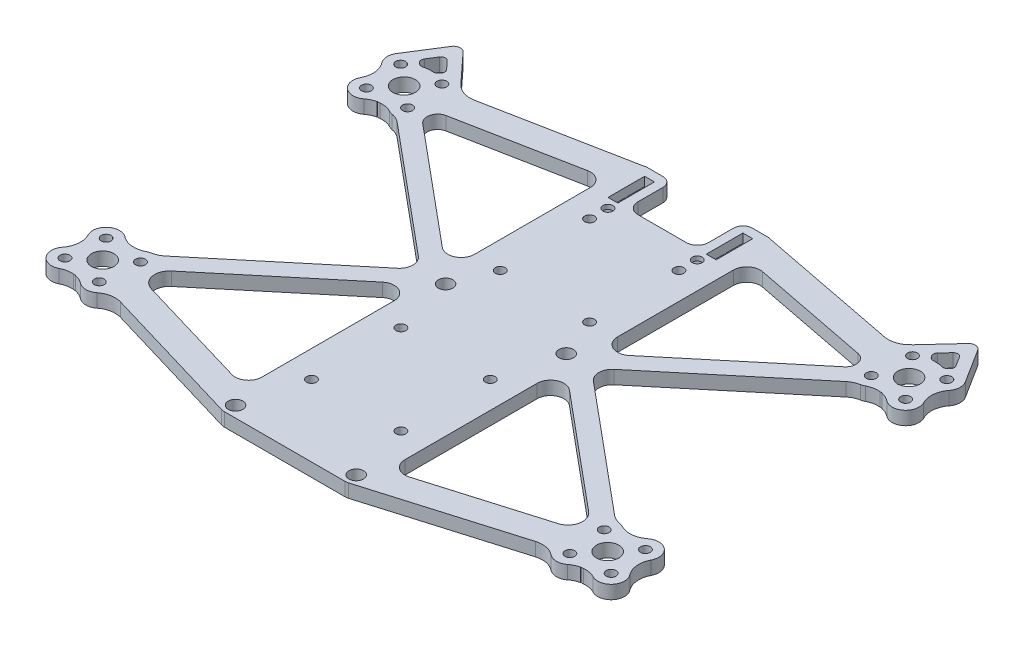
SolidWorks part; units mm, degrees
ref_plane "Front Plane" through (0, 0, 0) normal (0, 0, 1) x (1, 0, 0)
ref_plane "Top Plane" through (0, 0, 0) normal (0, 1, 0) x (1, 0, 0)
ref_plane "Right Plane" through (0, 0, 0) normal (1, 0, 0) x (0, 0, -1)
sketch "Sketch1" plane through (0, 0, 0) normal (0, 1, 0) x (1, 0, 0)
  line L0 (0, 42.225) -> (0, -42.225) construction
  line L1 (16, 42.225) -> (-16, 42.225)
  line L2 (16, 42.225) -> (16, -42.225)
  line L3 (16, -42.225) -> (-16, -42.225)
  line L4 (-16, 42.225) -> (-16, -42.225)
  line L5 (16, 42.225) -> (-16, -42.225) construction
  line L6 (16, -42.225) -> (-16, 42.225) construction
  line L12 (-12.1, 50.425) -> (-12.1, 52.425) construction
  line L17 (-11, 52.425) -> (-11, 42.225) construction
  line L18 (-7.9, 42.225) -> (-14.1, 42.225)
  line L20 (-10, 36) -> (10, 36)
  line L21 (-10, 36) -> (-10, 16)
  line L22 (-10, 16) -> (10, 16)
  line L23 (10, 36) -> (10, 16)
  line L24 (-10, 36) -> (10, 16) construction
  line L25 (-10, 16) -> (10, 36) construction
  line L26 (-14.5, 10.775) -> (14.5, 10.775)
  line L27 (-14.5, 10.775) -> (-14.5, 41.225)
  line L28 (-14.5, 41.225) -> (14.5, 41.225)
  line L29 (14.5, 10.775) -> (14.5, 41.225)
  line L30 (-14.5, 10.775) -> (14.5, 41.225) construction
  line L31 (-14.5, 41.225) -> (14.5, 10.775) construction
  line L32 (-10, -6.225) -> (10, -6.225)
  line L33 (-10, -6.225) -> (-10, -26.225)
  line L34 (-10, -26.225) -> (10, -26.225)
  line L35 (10, -6.225) -> (10, -26.225)
  line L36 (-10, -6.225) -> (10, -26.225) construction
  line L37 (-10, -26.225) -> (10, -6.225) construction
  line L38 (-15.75, -36.225) -> (15.75, -36.225)
  line L39 (-15.75, -36.225) -> (-15.75, 3.775)
  line L40 (-15.75, 3.775) -> (15.75, 3.775)
  line L41 (15.75, -36.225) -> (15.75, 3.775)
  line L42 (-15.75, -36.225) -> (15.75, 3.775) construction
  line L43 (-15.75, 3.775) -> (15.75, -36.225) construction
  line L48 (-7.9, 42.225) -> (-7.9, 52.425)
  line L49 (-7.9, 52.425) -> (-14.1, 52.425)
  line L59 (-14.1, 42.225) -> (-14.1, 52.425)
  line L63 (-12.1, 50.425) -> (-9.9, 50.425)
  line L64 (-12.1, 50.425) -> (-12.1, 42.225)
  line L65 (-12.1, 42.225) -> (-9.9, 42.225)
  line L66 (-9.9, 50.425) -> (-9.9, 42.225)
  line L67 (-12.1, 50.425) -> (-9.9, 42.225) construction
  line L68 (-12.1, 42.225) -> (-9.9, 50.425) construction
  line L69 (-12.1, 50.425) -> (-14.1, 50.425) construction
  line L74 (7.9, 42.225) -> (14.1, 42.225)
  line L75 (14.1, 42.225) -> (14.1, 52.425)
  line L76 (7.9, 52.425) -> (14.1, 52.425)
  line L77 (7.9, 42.225) -> (7.9, 52.425)
  line L78 (12.1, 50.425) -> (9.9, 50.425)
  line L79 (12.1, 50.425) -> (12.1, 42.225)
  line L80 (12.1, 42.225) -> (9.9, 42.225)
  line L81 (9.9, 50.425) -> (9.9, 42.225)
  line L82 (-14.5, 10.775) -> (-14.5, 3.775) construction
  line L83 (-14.5, 7.275) -> (16, 7.275) construction
  line L89 (-13.5, -37.225) -> (-16, -37.225) construction
  line L94 (-14.1, 52.425) -> (-16, 52.425)
  line L95 (-14.1, 52.425) -> (-14.1, 42.225)
  line L96 (-14.1, 42.225) -> (-16, 42.225)
  line L97 (-16, 52.425) -> (-16, 42.225)
  line L98 (14.1, 52.425) -> (16, 52.425)
  line L99 (14.1, 52.425) -> (14.1, 42.225)
  line L100 (14.1, 42.225) -> (16, 42.225)
  line L101 (16, 52.425) -> (16, 42.225)
  circle A3 centre (-10, 36) radius 1.1
  circle A4 centre (10, 36) radius 1.1
  circle A5 centre (10, 16) radius 1.1
  circle A6 centre (-10, 16) radius 1.1
  circle A7 centre (-10, -6.225) radius 1.1
  circle A8 centre (10, -6.225) radius 1.1
  circle A9 centre (10, -26.225) radius 1.1
  circle A10 centre (-10, -26.225) radius 1.1
  circle A37 centre (-13.5, 7.275) radius 2.5
  circle A38 centre (-13.5, 7.275) radius 1.625
  circle A39 centre (13.5, 7.275) radius 1.625
  circle A40 centre (-13.5, -39.725) radius 2.5
  circle A41 centre (-13.5, -39.725) radius 1.625
  circle A42 centre (13.5, -39.725) radius 1.625
  point P0 (0, 0)
  point P8 (0, 0)
  point P16 (0, 26)
  point P26 (0, 26)
  point P31 (0, -16.225)
  point P36 (0, -16.225)
  point P61 (-11, 46.325)
  dimension "D3" = 2
  dimension "D17" = 2.2
  dimension "D22" = 5
  dimension "D23" = 3.25
  dimension "D8" = 32
  dimension "D9" = 22
  dimension "D10" = 20
  dimension "D11" = 29
  dimension "D12" = 30.45
  dimension "D13" = 40
  dimension "D14" = 31.5
  dimension "D15" = 1
  dimension "D16" = 7
  dimension "D18" = 2.2
  dimension "D20" = 8.2
  dimension "D24" = 1
extrude "Base shape" add sketch "Sketch1" along normal blind 2 contours L63 L66 L1 L48 L49 L59 L18 L64 | L81 L78 L79 L1 L75 L76 L77 | L94 L97 L1 L59 | L101 L98 L75 L1 | L1 L4 L3 L2 | A4 | A3 | A7 | A8 | A9 | A10 | A5 | A6 | A39 | A38 | A41 | A42 region at (15.05, 0, -47.325) region at (13.1, 0, -42.3444) region at (-8.9, 0, -42.3444) region at (-15.05, 0, -47.325)
sketch "Sketch2" plane through (0, 0, 0) normal (0, -1, 0) x (1, 0, 0)
  line L0 (-12.1, -42.225) -> (-9.9, -50.425) construction
  line L1 (12.1, -42.225) -> (9.9, -50.425) construction
  line L4 (12.1, -42.225) -> (9.9, -42.225)
  line L5 (12.1, -50.425) -> (12.1, -42.225)
  line L6 (9.9, -50.425) -> (12.1, -50.425)
  line L7 (9.9, -42.225) -> (9.9, -50.425)
  line L8 (12.1, -42.225) -> (9.9, -42.225)
  line L9 (12.1, -50.425) -> (12.1, -42.225)
  line L10 (9.9, -50.425) -> (12.1, -50.425)
  line L11 (9.9, -42.225) -> (9.9, -50.425)
  line L12 (-9.9, -42.225) -> (-12.1, -42.225)
  line L13 (-9.9, -50.425) -> (-9.9, -42.225)
  line L14 (-12.1, -50.425) -> (-9.9, -50.425)
  line L15 (-12.1, -42.225) -> (-12.1, -50.425)
  line L16 (-9.9, -42.225) -> (-12.1, -42.225)
  line L17 (-9.9, -50.425) -> (-9.9, -42.225)
  line L18 (-12.1, -50.425) -> (-9.9, -50.425)
  line L19 (-12.1, -42.225) -> (-12.1, -50.425)
  circle A0 centre (-11, -46.325) radius 1.1
  circle A1 centre (11, -46.325) radius 1.1
  dimension "D1" = 0
  dimension "D2" = 0
extrude "Camera mount pockets" add sketch "Sketch2" against normal offset from surface (1 mm away) 1 contours A0 L19 | A0 L17 | A1 L9 | A1 L11 region at (11, 0, -43.8523) region at (11, 0, -48.7977) region at (-11, 0, -43.8523) region at (-11, 0, -48.7977) up to face at (11, 2, -46.325)
fillet "Main fillets" radius 2.5 6 edges at (7.9, 1, -42.225) (-7.9, 1, -42.225) (-16, 1, -52.425) (16, 1, -52.425) (-16, 1, 42.225) (16, 1, 42.225)
fillet "Inner camera mount fillets" radius 2.1 2 edges at (-7.9, 1, -52.425) (7.9, 1, -52.425)
sketch "Sketch3" plane through (0, 2, 0) normal (0, 1, 0) x (1, 0, 0)
  line L6 (12.1, 42.225) -> (12.1, 50.425)
  line L7 (9.9, 42.225) -> (12.1, 42.225)
  line L8 (-10, 52.425) -> (-13.5, 52.425)
  line L9 (-16, 49.925) -> (-16, -39.725)
  line L10 (-13.5, -42.225) -> (13.5, -42.225)
  line L11 (16, -39.725) -> (16, 49.925)
  line L12 (13.5, 52.425) -> (10, 52.425)
  line L13 (7.9, 50.325) -> (7.9, 44.725)
  line L14 (5.4, 42.225) -> (-5.4, 42.225)
  line L15 (-7.9, 44.725) -> (-7.9, 50.325)
  line L16 (-10, 52.425) -> (-13.5, 52.425)
  line L17 (-16, 49.925) -> (-16, -39.725)
  line L18 (-13.5, -42.225) -> (13.5, -42.225)
  line L19 (16, -39.725) -> (16, 49.925)
  line L20 (13.5, 52.425) -> (10, 52.425)
  line L21 (7.9, 50.325) -> (7.9, 44.725)
  line L22 (5.4, 42.225) -> (-5.4, 42.225)
  line L23 (-7.9, 44.725) -> (-7.9, 50.325)
  line L24 (9.9, 50.425) -> (9.9, 42.225)
  line L25 (12.1, 50.425) -> (9.9, 50.425)
  line L26 (12.1, 42.225) -> (12.1, 50.425)
  line L27 (9.9, 42.225) -> (12.1, 42.225)
  line L28 (9.9, 50.425) -> (9.9, 42.225)
  line L29 (12.1, 50.425) -> (9.9, 50.425)
  line L30 (-9.9, 42.225) -> (-9.9, 50.425)
  line L31 (-12.1, 42.225) -> (-9.9, 42.225)
  line L32 (-12.1, 50.425) -> (-12.1, 42.225)
  line L33 (-9.9, 50.425) -> (-12.1, 50.425)
  line L34 (-9.9, 42.225) -> (-9.9, 50.425)
  line L35 (-12.1, 42.225) -> (-9.9, 42.225)
  line L36 (-12.1, 50.425) -> (-12.1, 42.225)
  line L37 (-9.9, 50.425) -> (-12.1, 50.425)
  circle A0 centre (13.5, -39.725) radius 1.625 construction
  circle A1 centre (-13.5, -39.725) radius 1.625 construction
  circle A2 centre (-13.5, 7.275) radius 1.625 construction
  circle A3 centre (-10, -6.225) radius 1.1 construction
  circle A4 centre (-10, -26.225) radius 1.1 construction
  circle A5 centre (10, -26.225) radius 1.1 construction
  circle A6 centre (10, -6.225) radius 1.1 construction
  circle A7 centre (13.5, 7.275) radius 1.625 construction
  arc A8 (-13.5, 52.425) -> (-16, 49.925) centre (-13.5, 49.925) ccw
  arc A9 (-16, -39.725) -> (-13.5, -42.225) centre (-13.5, -39.725) ccw
  arc A10 (13.5, -42.225) -> (16, -39.725) centre (13.5, -39.725) ccw
  arc A11 (16, 49.925) -> (13.5, 52.425) centre (13.5, 49.925) ccw
  arc A12 (-7.9, 50.325) -> (-10, 52.425) centre (-10, 50.325) ccw
  arc A13 (5.4, 42.225) -> (7.9, 44.725) centre (5.4, 44.725) ccw
  arc A14 (-7.9, 44.725) -> (-5.4, 42.225) centre (-5.4, 44.725) ccw
  arc A15 (-7.9, 50.325) -> (-10, 52.425) centre (-10, 50.325) ccw
  arc A16 (-13.5, 52.425) -> (-16, 49.925) centre (-13.5, 49.925) ccw
  arc A17 (-16, -39.725) -> (-13.5, -42.225) centre (-13.5, -39.725) ccw
  arc A18 (13.5, -42.225) -> (16, -39.725) centre (13.5, -39.725) ccw
  arc A19 (16, 49.925) -> (13.5, 52.425) centre (13.5, 49.925) ccw
  arc A21 (5.4, 42.225) -> (7.9, 44.725) centre (5.4, 44.725) ccw
  arc A22 (-7.9, 44.725) -> (-5.4, 42.225) centre (-5.4, 44.725) ccw
  circle A24 centre (-10, 16) radius 1.1 construction
  circle A25 centre (-10, 36) radius 1.1 construction
  circle A26 centre (10, 36) radius 1.1 construction
  circle A27 centre (10, 16) radius 1.1 construction
  circle A28 centre (10, 16) radius 1.1
  circle A29 centre (10, 36) radius 1.1
  circle A30 centre (-10, 36) radius 1.1
  circle A31 centre (-10, 16) radius 1.1
  circle A32 centre (13.5, 7.275) radius 1.625
  circle A33 centre (10, -6.225) radius 1.1
  circle A34 centre (10, -26.225) radius 1.1
  circle A35 centre (-10, -26.225) radius 1.1
  circle A36 centre (-10, -6.225) radius 1.1
  circle A37 centre (13.5, -39.725) radius 1.625
  circle A38 centre (-13.5, -39.725) radius 1.625
  circle A39 centre (-13.5, 7.275) radius 1.625
  arc A48 (10, 52.425) -> (7.9, 50.325) centre (10, 50.325) ccw
  arc A49 (10, 52.425) -> (7.9, 50.325) centre (10, 50.325) ccw
  dimension "D1" = 0
  dimension "D2" = 0
  dimension "D3" = 0
extrude "Thicker base" add sketch "Sketch3" along normal blind 1
sketch "Sketch4" plane through (0, 0, 0) normal (0, -1, 0) x (1, 0, 0)
  line L0 (0, 13.9568) -> (0, -8.6953) construction
  line L1 (-14.1, -38.5) -> (-5.9, -38.5)
  line L2 (-14.1, -38.5) -> (-14.1, -41.7)
  line L3 (-14.1, -41.7) -> (-5.9, -41.7)
  line L4 (-5.9, -38.5) -> (-5.9, -41.7)
  line L5 (-10, -38.5) -> (-10, -41.7) construction
  line L7 (14.1, -38.5) -> (5.9, -38.5)
  line L8 (14.1, -38.5) -> (14.1, -41.7)
  line L9 (14.1, -41.7) -> (5.9, -41.7)
  line L10 (5.9, -38.5) -> (5.9, -41.7)
  line L11 (-14.1, -38.5) -> (-10.9, -41.7) construction
  line L12 (-14.1, -40.1) -> (-5.9, -40.1) construction
  circle A0 centre (-10, -36) radius 2
  circle A1 centre (-13.3929, -39.2071) radius 1
  circle A2 centre (-13.3929, -40.9929) radius 1
  circle A3 centre (-6.6071, -39.2071) radius 1
  circle A4 centre (-6.6071, -40.9929) radius 1
  circle A5 centre (6.6071, -40.9929) radius 1
  circle A6 centre (6.6071, -39.2071) radius 1
  circle A7 centre (13.3929, -39.2071) radius 1
  circle A8 centre (13.3929, -40.9929) radius 1
  point P9 (-10, -38)
  dimension "D5" = 4
  dimension "D7" = 2
  dimension "D1" = 8.2
  dimension "D2" = 3.2
  dimension "D3" = 10
  dimension "D4" = 0.5
  dimension "D6" = 45
extrude "Battery holder pockets" cut sketch "Sketch4" against normal offset from surface (2 mm away) 1 contours A2 L2 | A2 L3 | L2 A1 | L1 A1 | A3 L4 | A3 L1 | L4 A4 | L3 A4 | A5 L9 | A5 L10 | L10 A6 | L7 A6 | A7 L7 | A7 L8 | L8 A8 | L9 A8 | L3 L4 L1 L2 | L9 L10 L7 L8 region at (-13.3929, 0, -38.3812) region at (-14.2188, 0, -39.2071) region at (-6.6071, 0, -38.3812) region at (-14.2188, 0, -40.9929) region at (-5.7812, 0, -39.2071) region at (-13.3929, 0, -41.8188) region at (-6.6071, 0, -41.8188) region at (-5.7812, 0, -40.9929) region at (14.2188, 0, -39.2071) region at (13.3929, 0, -38.3812) region at (6.6071, 0, -38.3812) region at (14.2188, 0, -40.9929) region at (5.7812, 0, -39.2071) region at (13.3929, 0, -41.8188) region at (6.6071, 0, -41.8188) region at (5.7812, 0, -40.9929) up to face at (-13.5, 3, 41.35)
sketch "Sketch5" plane through (0, 2, 0) normal (0, -1, 0) x (1, 0, 0)
  line L0 (-10, -38.5) -> (-10, -41.7) construction
  line L1 (-12.6858, -38.5) -> (-7.3142, -38.5) construction
  line L2 (-12.6858, -41.7) -> (-7.3142, -41.7) construction
  line L3 (0, 5.9884) -> (0, -5.6723) construction
  circle A0 centre (-10, -40.1) radius 1.1
  circle A1 centre (10, -40.1) radius 1.1
  dimension "D1" = 2.2
extrude "Battery holder holes" cut sketch "Sketch5" against normal up to next
sketch "Sketch6" [suppressed] plane through (0, 0, 0) normal (0, -1, 0) x (1, 0, 0)
  line L0 (0, -5.1) -> (0, 9.653) construction
  line L8 (-13.5, -7.275) -> (13.5, -7.275) construction
  line L10 (-16, -23.775) -> (16, -23.775) construction
  line L11 (-16, -49.925) -> (-16, 39.725) construction
  line L12 (16, -49.925) -> (16, 39.725) construction
  line L13 (17.5, -32.275) -> (19, -32.275)
  line L14 (16, -35.275) -> (19, -35.275)
  line L15 (16, -35.275) -> (16, -12.275)
  line L16 (16, -12.275) -> (19, -12.275)
  line L17 (19, -35.275) -> (19, -12.275)
  line L18 (16, -35.275) -> (19, -12.275) construction
  line L19 (16, -12.275) -> (19, -35.275) construction
  line L20 (16, -33.775) -> (17.5, -33.775)
  line L21 (16, -33.775) -> (16, -13.775)
  line L22 (16, -13.775) -> (17.5, -13.775)
  line L23 (17.5, -33.775) -> (17.5, -13.775)
  line L24 (16, -33.775) -> (17.5, -13.775) construction
  line L25 (16, -13.775) -> (17.5, -33.775) construction
  line L26 (17.5, -15.275) -> (19, -15.275)
  line L27 (-17.5, -32.275) -> (-19, -32.275)
  line L28 (-17.5, -15.275) -> (-19, -15.275)
  line L29 (-16, -33.775) -> (-16, -13.775)
  line L30 (-16, -33.775) -> (-17.5, -33.775)
  line L31 (-17.5, -33.775) -> (-17.5, -13.775)
  line L32 (-16, -13.775) -> (-17.5, -13.775)
  line L33 (-16, -35.275) -> (-16, -12.275)
  line L34 (-16, -35.275) -> (-19, -35.275)
  line L35 (-19, -35.275) -> (-19, -12.275)
  line L36 (-16, -12.275) -> (-19, -12.275)
  line L37 (16, 20.725) -> (19, 20.725)
  line L38 (16, 20.725) -> (16, -2.275)
  line L39 (16, -2.275) -> (19, -2.275)
  line L40 (19, 20.725) -> (19, -2.275)
  line L41 (16, 19.225) -> (17.5, 19.225)
  line L42 (16, 19.225) -> (16, -0.775)
  line L43 (16, -0.775) -> (17.5, -0.775)
  line L44 (17.5, 19.225) -> (17.5, -0.775)
  line L45 (17.5, 0.725) -> (19, 0.725)
  line L46 (17.5, 17.725) -> (19, 17.725)
  line L47 (-17.5, 17.725) -> (-19, 17.725)
  line L48 (-17.5, 0.725) -> (-19, 0.725)
  line L49 (-16, 19.225) -> (-16, -0.775)
  line L50 (-16, 19.225) -> (-17.5, 19.225)
  line L51 (-17.5, 19.225) -> (-17.5, -0.775)
  line L52 (-16, -0.775) -> (-17.5, -0.775)
  line L53 (-16, 20.725) -> (-16, -2.275)
  line L54 (-16, 20.725) -> (-19, 20.725)
  line L55 (-19, 20.725) -> (-19, -2.275)
  line L56 (-16, -2.275) -> (-19, -2.275)
  point P19 (17.5, -23.775)
  point P25 (16.75, -23.775)
  line M18 (16, -49.925) -> (16, 39.725)
  line M22 (-16, 39.725) -> (-16, -49.925)
  dimension "D1" = 10
  dimension "D4" = 23
  dimension "D5" = 3
  dimension "D6" = 1.5
  dimension "D7" = 20
  dimension "D8" = 1.5
extrude "Strap holders" [suppressed] add sketch "Sketch6" against normal up to surface (2 mm away) contours L23 L20 L14 L17 L13 M18 | L23 L26 L17 L16 L22 M18 | L45 L44 L43 L39 L40 M18 | L44 L46 L40 L37 L38 L41 | L54 L55 L47 L51 L50 M22 | L56 L52 L51 L48 L55 M22 | L36 L35 L28 L31 L32 M22 | L35 L34 L30 L31 L27 M22 up to face at (-10, 2, -41.2)
fillet "Strap holder fillets" [suppressed] radius 0.75
sketch "Sketch7" plane through (0, 3, 0) normal (0, 1, 0) x (1, 0, 0)
  line L0 (-56.5, 41) -> (-16, 48.8822) construction
  line L1 (56.5, -41) -> (-56.5, -41)
  line L2 (56.5, -41) -> (56.5, 41)
  line L3 (56.5, 41) -> (-56.5, 41)
  line L4 (-56.5, -41) -> (-56.5, 41)
  line L5 (56.5, -41) -> (-56.5, 41) construction
  line L6 (56.5, 41) -> (-56.5, -41) construction
  line L7 (-16, 49.925) -> (-16, -39.725) construction
  line L8 (-55.9269, 38.0553) -> (-15.4269, 45.9374)
  line L9 (-48.7441, 45.5657) -> (-13.5, 52.425)
  line L10 (-57.0731, 43.9447) -> (-16.5731, 51.8269) construction
  line L11 (-13.5, 7.275) -> (13.5, 7.275) construction
  line L12 (-62.2591, 34.0839) -> (-50.7409, 47.9161) construction
  line L13 (-56.5, 41) -> (-16, 7.275) construction
  line L14 (-57.7798, 39.4631) -> (-17.2798, 5.7381)
  line L15 (-55.2202, 42.5369) -> (-14.7202, 8.8119)
  line L16 (-17.2798, 5.7381) -> (-16, 4.6724)
  line L17 (-56.5, 41) -> (-61.1107, 44.8394) construction
  line L18 (-56.5, 50) -> (-56.5, 32) construction
  line L19 (-61.1107, 44.8394) -> (-52.6606, 45.6107) construction
  line L20 (-56.8857, 45.2251) -> (-57.6128, 53.192) construction
  line L21 (-58.8813, 53.9926) -> (-63.553, 46.5906)
  line L22 (-56.5103, 54.209) -> (-50.5757, 47.7751)
  line L23 (-57.4765, 51.6982) -> (-60.0373, 47.6408)
  line L24 (-57.4765, 51.6982) -> (-54.2235, 48.1715)
  line L25 (-57.7798, -24.9131) -> (-17.2798, 8.8119)
  line L26 (-55.2202, -27.9869) -> (-14.7202, 5.7381)
  line L27 (-56.5, -26.45) -> (-16, -38.462) construction
  line L28 (-49.218, -31.7389) -> (-14.2109, -42.1218)
  line L29 (-55.647, -23.5738) -> (-15.147, -35.5858)
  line L30 (-57.353, -29.3262) -> (-16.853, -41.3382) construction
  circle A0 centre (-56.5, 41) radius 38.1
  circle A1 centre (-56.5, 41) radius 9
  circle A2 centre (-56.5, 41) radius 6
  circle A3 centre (-52.6606, 45.6107) radius 1.1
  circle A4 centre (-60.3394, 36.3893) radius 1.1
  circle A5 centre (-61.1107, 44.8394) radius 1.1
  circle A6 centre (-51.8893, 37.1606) radius 1.1
  circle A7 centre (-61.1107, 44.8394) radius 3
  circle A8 centre (-52.6606, 45.6107) radius 3
  circle A9 centre (-60.3394, 36.3893) radius 3
  circle A10 centre (-51.8893, 37.1606) radius 3
  circle A12 centre (-56.5, 41) radius 2.5
  circle A13 centre (-57.6128, 53.192) radius 1.5
  circle A14 centre (-67.319, 40.0125) radius 4.864
  circle A15 centre (-55.5125, 30.181) radius 4.864
  circle A16 centre (-46.7947, 50.9004) radius 4.864
  circle A17 centre (-53.3325, 29.4302) radius 4.864
  circle A18 centre (-45.6353, 37.6419) radius 2.3718
  circle A20 centre (-56.5, -26.45) radius 6
  circle A21 centre (-51.8893, -22.6106) radius 1.1
  circle A22 centre (-60.3394, -21.8393) radius 1.1
  circle A23 centre (-61.1107, -30.2894) radius 1.1
  circle A24 centre (-52.6606, -31.0607) radius 1.1
  circle A25 centre (-52.6606, -31.0607) radius 3
  circle A26 centre (-51.8893, -22.6106) radius 3
  circle A27 centre (-56.5, -26.45) radius 2.5
  circle A28 centre (-61.1107, -30.2894) radius 3
  circle A29 centre (-67.319, -25.4625) radius 4.864
  circle A30 centre (-60.3394, -21.8393) radius 3
  circle A31 centre (-55.5125, -15.631) radius 4.864
  circle A32 centre (-53.3325, -14.8802) radius 4.864
  circle A34 centre (-56.5, -26.45) radius 9
  circle A35 centre (-57.4875, -37.269) radius 4.864
  arc A37 (-16, -39.725) -> (-13.5, -42.225) centre (-13.5, -39.725) ccw construction
  circle A38 centre (-47.7979, -37.1938) radius 4.8259
  circle A39 centre (-44.585, -23.4182) radius 3.2947
  point P0 (0, 0)
  point P36 (-51.8893, 37.1606)
  point P54 (-57.4765, 51.6982)
  arc M23 (-13.5, 52.425) -> (-16, 49.925) centre (-13.5, 49.925) ccw
  line M24 (-16, 49.925) -> (-16, -39.725)
  arc M25 (-16, -39.725) -> (-13.5, -42.225) centre (-13.5, -39.725) ccw
  dimension "D3" = 76.2
  dimension "D4" = 12
  dimension "D5" = 3
  dimension "D10" = 2.2
  dimension "D11" = 5
  dimension "D12" = 3
  dimension "D1" = 113
  dimension "D2" = 82
  dimension "D13" = 8
  dimension "D6" = 3
  dimension "D7" = 3
  dimension "D8" = 2
  dimension "D9" = 2
  dimension "D14" = 3
  dimension "D15" = 3
extrude "Arms" add sketch "Sketch7" against normal up to surface (3 mm away) contours A13 | A13 L21 A1 L23 | A13 L24 A1 L22 | A12 L15 L3 A2 A8 A7 A9 L4 L14 | A10 L14 L4 A2 | A12 L4 L14 A10 L15 L3 | A12 L3 L15 | A10 A2 L3 L15 | A7 L23 A1 | A8 A1 L24 | A14 A2 A7 | A14 A9 A2 | A15 L4 A2 A9 | A15 A10 A2 | A8 A2 L3 A1 | A16 A1 L9 | A1 L3 L8 A0 L9 | A10 L8 A1 L3 A2 | A10 L15 A1 L8 | A10 A1 L15 | A10 L14 A1 | A17 A1 L14 A10 | A1 L14 A0 L15 | A17 L14 A1 | A0 L14 L16 L15 M24 | A0 L8 L9 M24 M23 | A1 L8 L3 | A18 L8 A1 | A18 A1 L15 | L25 A34 L26 L16 L14 | L29 A34 L28 L1 M25 M24 | A34 L29 A26 A20 A25 | A34 L26 A26 L29 | A38 L28 A34 | A34 A26 L26 | A34 L25 A26 | A32 A34 L25 | A34 A32 A26 L25 | A26 A31 A20 | L4 A31 A30 A20 | A20 A30 A28 L4 A27 L25 | L25 A26 A20 L4 | A20 A31 L4 | L4 A27 L26 A26 L25 | L26 A27 L4 A20 A25 A26 | A35 A25 A20 L4 | A35 A20 A28 | A20 A29 A28 | A20 A30 A29 | A39 L26 A34 | A39 A34 L29 | L25 A27 L4 | L1 L28 M25 | A7 | A5 | A8 | A3 | A10 | A6 | A9 | A4 | A25 | A24 | A26 | A21 | A28 | A23 | A30 | A22 region at (-16.139, 3, 41.3276) region at (-32.0548, 3, 33.7211) region at (-48.9183, 3, 32.3052) region at (-17.512, 3, -48.8664) region at (-21.642, 3, -11.8743) region at (-49.1658, 3, 28.1048) region at (-47.1131, 3, 25.7411) region at (-33.5979, 3, 7.3867) region at (-45.287, 3, -40.5598) region at (-33.1819, 3, -45.6059) region at (-38.4384, 3, -25.9598) region at (-48.6014, 3, 24.4797) region at (-47.909, 3, 22.4325) region at (-49.0457, 3, -40.2446) region at (-49.1442, 3, -43.1485) region at (-47.3222, 3, -39.4546) region at (-48.0479, 3, -36.9785) region at (-55.5626, 3, 32.6566) region at (-48.8372, 3, 22.0461) region at (-51.6653, 3, -40.5782) region at (-51.9373, 3, -41.1697) region at (-48.3887, 3, -46.1037) region at (-48.5353, 3, -38.5539) region at (-48.8372, 3, -36.5961) region at (-50.8649, 3, -33.6569) region at (-58.5204, 3, 32.3845) region at (-53.3964, 3, 28.1246) region at (-50.7815, 3, 19.7112) region at (-50.8649, 3, 19.1069) region at (-54.4455, 3, -39.1872) region at (-53.806, 3, -41.1887) region at (-50.7815, 3, -34.2612) region at (-51.5106, 3, -34.0266) region at (-62.7022, 3, 27.3626) region at (-58.1278, 3, 31.2511) region at (-54.4187, 3, 24.7209) region at (-51.5106, 3, 19.4766) region at (-54.8114, 3, -50.9666) region at (-62.4345, 3, 24.4296) region at (-53.9078, 3, -49.0743) region at (-57.6128, 3, -53.192) region at (-57.4374, 3, 20.2434) region at (-57.4374, 3, -34.7934) region at (-54.4796, 3, -35.0655) region at (-56.5422, 3, 23.9165) region at (-55.689, 3, 21.824) region at (-54.4796, 3, 20.5155) region at (-55.689, 3, -36.374) region at (-60.5112, 3, -48.4716) region at (-59.9651, 3, -50.4962) region at (-56.3638, 3, 20.4356) region at (-62.4345, 3, -38.9796) region at (-62.7022, 3, -41.9126) up to face at (10, 0, -40.1)
fillet "Motor protector fillets" radius 1 5 edges at (-54.2235, 1.5, -48.1715) (-55.3727, 1.5, -46.8931) (-58.6756, 1.5, -46.5917) (-60.0373, 1.5, -47.6408) (-57.4765, 1.5, -51.6982)
mirror "Arms mirror" about plane through (0, 0, 0) normal (1, 0, 0) of "Arms", "Motor protector fillets"
fillet "Arm fillets" radius 3 10 edges at (-16, 1.5, 35.3328) (-16, 1.5, -4.6724) (-16, 1.5, -9.8776) (-16, 1.5, -45.8259) (-19.1255, 1.5, -7.275) (16, 1.5, -9.8776) (16, 1.5, 35.3328) (19.1255, 1.5, -7.275) (16, 1.5, -4.6724) (16, 1.5, -45.8259)
